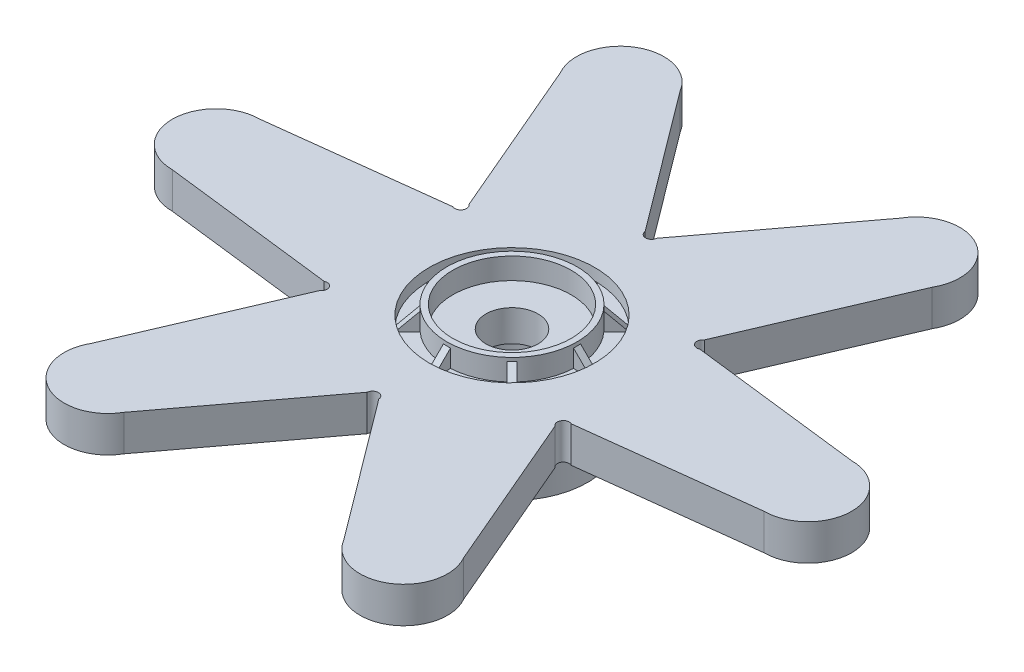
SolidWorks part; units mm, degrees
ref_plane "Front Plane" through (0, 0, 0) normal (0, 0, 1) x (1, 0, 0)
ref_plane "Top Plane" through (0, 0, 0) normal (0, 1, 0) x (1, 0, 0)
ref_plane "Right Plane" through (0, 0, 0) normal (1, 0, 0) x (0, 0, -1)
sketch "Sketch1" plane through (0, 0, 0) normal (0, 1, 0) x (1, 0, 0)
  line L0 (5.7752, -3.8298) -> (0, 0)
  line L1 (6.3503, 3.495) -> (6.3503, 3.8298)
  line L2 (6.3497, -3.4899) -> (15.8747, -2.3469)
  line L3 (6.3503, 3.495) -> (15.8747, 2.3521)
  line L4 (5.7752, 3.8298) -> (0, 0)
  line L5 (6.3503, 3.8298) -> (5.7752, 3.8298)
  line L6 (6.3497, -3.4899) -> (6.3497, -3.8298)
  line L7 (6.3497, -3.8298) -> (5.7752, -3.8298)
  arc A0 (15.8747, -2.3469) -> (15.8747, 2.3521) centre (15.8747, 0.0026) ccw
  dimension "D2" = 4.699
extrude "Extrude4" add sketch "Sketch1" along normal blind 1.9304
sketch "Sketch2" plane through (0, 1.9304, 0) normal (0, 1, 0) x (-1, 0, 0)
  circle A0 centre (-6.3426, -4.1499) radius 0.6604
  circle A1 centre (-6.3426, 4.1499) radius 0.6604
  dimension "D1" = 1.3208
extrude "Cut-Extrude1" cut sketch "Sketch2" against normal through all contours A1 | A0
ref_axis "Axis1" through (0, 0, 0) along (0, 1, 0)
pattern_circular "CirPattern4" count 6 over 360 about axis through (0, 0, 0) along (0, 1, 0) of "Extrude4"
sketch "Sketch3" plane through (0, 1.9304, 0) normal (0, 1, 0) x (-1, 0, 0)
  circle A0 centre (0, 0) radius 1.397
  dimension "D1" = 2.794
extrude "Cut-Extrude2" cut sketch "Sketch3" against normal blind 12.7 and the other way blind 12.7
sketch "Sketch4" plane through (0, 1.9304, 0) normal (0, 1, 0) x (-1, 0, 0)
  circle A0 centre (0, 0) radius 4.445
  dimension "D1" = 8.89
extrude "Cut-Extrude3" cut sketch "Sketch4" against normal blind 0.635
sketch "Sketch5" plane through (0, 1.2954, 0) normal (0, 1, 0) x (-1, 0, 0)
  circle A0 centre (0, 0) radius 3.4925
  circle A1 centre (0, 0) radius 3.175
  dimension "D1" = 6.985
  dimension "D2" = 6.35
extrude "Extrude5" add sketch "Sketch5" along normal blind 1.143 contours A1 | A0
sketch "Sketch8" plane through (0, 0, 0) normal (0, 0, 1) x (1, 0, 0)
  line L1 (4.445, 1.2954) -> (-4.445, 1.2954) construction
  line L4 (-3.4925, 2.2448) -> (-4.443, 1.2954)
rib "Rib10" sketch "Sketch8" sketch "Sketch8" thickness 0.381 extrusion direction parallel to sketch draft on no parameters "D1"=0.381
pattern_circular "CirPattern5" count 8 over 360 about axis through (0, 0, 0) along (0, 1, 0) of "Rib10"
sketch "Sketch10" plane through (0, 0, 0) normal (0, -1, 0) x (1, 0, 0)
  circle A0 centre (0, 0) radius 5.08
  dimension "D1" = 10.16
extrude "Extrude6" add sketch "Sketch10" along normal blind 0.762
fillet "Fillet2" radius 0.508 1 edges at (0, 0, 5.08)
sketch "Sketch11" plane through (0, -0.762, 0) normal (0, -1, 0) x (1, 0, 0)
  circle A0 centre (0, 0) radius 4.064
  dimension "D1" = 8.128
extrude "Extrude7" add sketch "Sketch11" along normal blind 3.048
fillet "Fillet3" radius 0.889 1 edges at (0, -0.762, -4.064)
sketch "Sketch12" plane through (0, -3.81, 0) normal (0, -1, 0) x (1, 0, 0)
  circle A0 centre (0, 0) radius 2.8575
  dimension "D1" = 5.715
extrude "Cut-Extrude5" cut sketch "Sketch12" against normal blind 3.429
sketch "Sketch14" plane through (0, -0.381, 0) normal (0, -1, 0) x (1, 0, 0)
  circle A0 centre (0, 0) radius 1.397
  dimension "D1" = 2.794
extrude "Cut-Extrude6" cut sketch "Sketch14" against normal through all
sketch "Sketch15" plane through (0, 1.9304, 0) normal (0, 1, 0) x (-1, 0, 0)
  circle A0 centre (-6.4872, -3.7519) radius 0.3175
  dimension "D1" = 0.635
extrude "Cut-Extrude7" cut sketch "Sketch15" against normal through all and the other way through all
pattern_circular "CirPattern7" count 6 over 360 about axis through (0, 0, 0) along (0, 1, 0) of "Cut-Extrude7"
